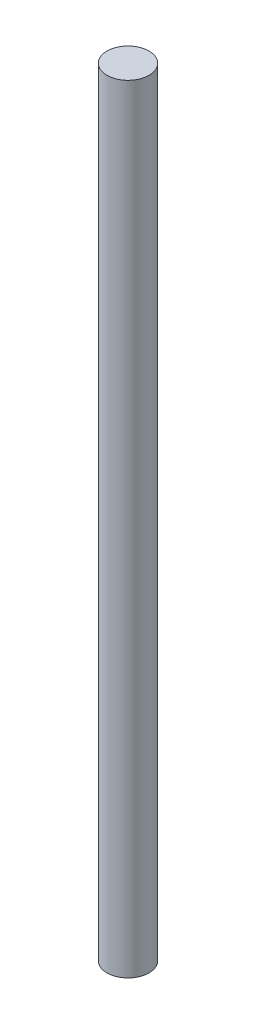
SolidWorks part; units mm, degrees
ref_plane "Front Plane" through (0, 0, 0) normal (0, 0, 1) x (1, 0, 0)
ref_plane "Top Plane" through (0, 0, 0) normal (0, 1, 0) x (1, 0, 0)
ref_plane "Right Plane" through (0, 0, 0) normal (1, 0, 0) x (0, 0, -1)
sketch "Sketch1" plane through (0, 0, 0) normal (0, 1, 0) x (1, 0, 0)
  circle A0 centre (0, 0) radius 12.5
  dimension "D1" = 25
extrude "Boss-Extrude1" add sketch "Sketch1" along normal blind 462.002
